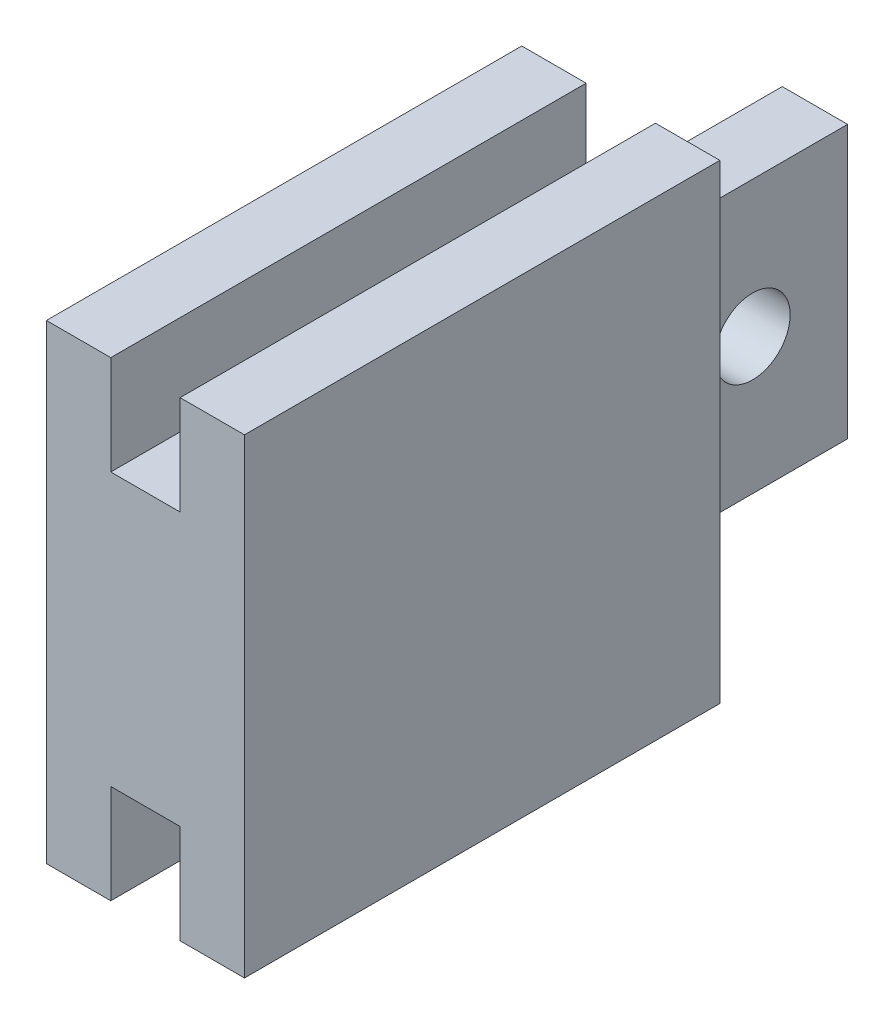
SolidWorks part; units mm, degrees
ref_plane "Front Plane" through (0, 0, 0) normal (1, 0, 0) x (0, 1, 0)
ref_plane "Top Plane" through (0, 0, 0) normal (0, 0, 1) x (0, 1, 0)
ref_plane "Right Plane" through (0, 0, 0) normal (0, 1, 0) x (-1, 0, 0)
sketch "Sketch1" plane through (0, 0, 0) normal (1, 0, 0) x (0, 1, 0)
  line L1 (0, 0) -> (23.75, 0)
  line L2 (0, 0) -> (0, 24)
  line L3 (0, 24) -> (23.75, 24)
  line L4 (23.75, 0) -> (23.75, 24)
  dimension "D1" = 23.75
  dimension "D2" = 24
extrude "Boss-Extrude1" add sketch "Sketch1" against normal blind 10
sketch "Sketch2" plane through (0, 0, 0) normal (0, -1, 0) x (1, 0, 0)
  line L1 (-10, 0) -> (-6.65, 0)
  line L2 (-10, 0) -> (-10, -9.8)
  line L3 (-10, -9.8) -> (-6.65, -9.8)
  line L4 (-6.65, 0) -> (-6.65, -9.8)
  line L5 (0, 0) -> (-3.35, 0)
  line L6 (0, 0) -> (0, -9.8)
  line L7 (0, -9.8) -> (-3.35, -9.8)
  line L8 (-3.35, 0) -> (-3.35, -9.8)
  line L9 (-6.65, -9.8) -> (-3.35, -9.8)
  line L10 (-6.65, -9.8) -> (-6.65, 0)
  line L11 (-6.65, 0) -> (-3.35, 0)
  line L12 (-3.35, -9.8) -> (-3.35, 0)
  line M12 (-10, 0) -> (0, 0)
  dimension "D1" = 9.8
  dimension "D2" = 3.35
  dimension "D3" = 3.35
extrude "Boss-Extrude2" add sketch "Sketch2" against normal through all contours L4 L9 L8 M12 region at (-5, 0, -4.9)
sketch "Sketch3" plane through (0, 0, 0) normal (0, -1, 0) x (1, 0, 0)
  line L0 (-3.35, 20.65) -> (-3.35, 3.35)
  line L1 (0, 24) -> (-10, 24)
  line L2 (0, 24) -> (0, 0)
  line L3 (0, 0) -> (-10, 0)
  line L4 (-10, 24) -> (-10, 0)
  line L5 (-3.35, 3.35) -> (-6.65, 3.35)
  line L6 (-6.65, 20.65) -> (-6.65, 3.35)
  line L7 (-3.35, 20.65) -> (-6.65, 20.65)
  line L9 (-6.65, 20.65) -> (-3.35, 20.65)
  line L10 (-6.65, 20.65) -> (-6.65, 24)
  line L11 (-6.65, 24) -> (-3.35, 24)
  line L12 (-3.35, 20.65) -> (-3.35, 24)
  dimension "D1" = 3.35
extrude "Boss-Extrude3" [suppressed] add sketch "Sketch3" along normal blind 4.9 contours L0 L7 L6 L5 | L10 L9 L12 L11
sketch "Sketch4" plane through (-6.65, 0, 0) normal (-1, 0, 0) x (0, -1, 0)
  line L0 (0, 0) -> (-23.75, 0) construction
  line L1 (-11.875, 0) -> (-23.75, 0)
  line L2 (-11.875, 0) -> (-11.875, -5)
  line L3 (-11.875, -5) -> (-23.75, -5)
  line L4 (-23.75, 0) -> (-23.75, -5)
  circle A0 centre (-11.875, -5) radius 1.9
  dimension "D2" = 3.8
extrude "Cut-Extrude1" cut sketch "Sketch4" against normal up to next contours A0
sketch "Sketch5" plane through (0, 23.75, 0) normal (0, 1, 0) x (-1, 0, 0)
  line L0 (3.25, 20.75) -> (3.25, 3.25)
  line L1 (0, 24) -> (10, 24)
  line L2 (0, 24) -> (0, 0)
  line L3 (0, 0) -> (10, 0)
  line L4 (10, 24) -> (10, 0)
  line L5 (3.25, 3.25) -> (6.75, 3.25)
  line L6 (6.75, 20.75) -> (6.75, 3.25)
  line L7 (3.25, 20.75) -> (6.75, 20.75)
  line L9 (3.25, 20.75) -> (6.75, 20.75)
  line L10 (3.25, 20.75) -> (3.25, 24)
  line L11 (3.25, 24) -> (6.75, 24)
  line L12 (6.75, 20.75) -> (6.75, 24)
  line L13 (3.25, 3.25) -> (6.75, 3.25)
  line L14 (3.25, 3.25) -> (3.25, -9.8)
  line L15 (3.25, -9.8) -> (6.75, -9.8)
  line L16 (6.75, 3.25) -> (6.75, -9.8)
  line M11 (3.35, 0) -> (3.35, -9.8)
  line M12 (3.35, -9.8) -> (6.65, -9.8)
  line M13 (6.65, -9.8) -> (6.65, 0)
  line M14 (6.65, 0) -> (10, 0)
  dimension "D1" = 3.25
extrude "Cut-Extrude2" cut sketch "Sketch5" against normal blind 5 contours L7 L12 L1 L10 | L7 L0 L5 L6 | L16 L5 L14 L3 M14 | L3 M11 M12 M13 region at (-5, 23.75, 12) region at (-5, 23.75, 22.375) region at (-5, 23.75, 1.625) region at (-5, 23.75, -4.9)
ref_plane "Plane1" through (0, 11.875, 0) normal (0, 1, 0) x (1, 0, 0)
mirror "Mirror1" about plane through (0, 11.875, 0) normal (0, 1, 0) of "Cut-Extrude2"
equation "\"whitekey_cutout_length\"= 101.5"
equation "\"key_mount_recess_length\"=50"
equation "\"key_mount_recess_height\"=12.5"
equation "\"key_mount_recess_depth\"=1.5"
equation "\"wall_thickness\"=10"
equation "\"guide_brace_height\"=20"
equation "\"guide_brace_thickness\"=2"
equation "\"dowel_recess_depth\"=10"
equation "\"dowel_recess_offset\"=3.25"
equation "\"base_mount_height\"=40"
equation "\"base_rear_length\"=80"
equation "\"base_front_length\"=111.5"
equation "\"screw_hole_wall_offset\"=7.25"
equation "\"screw_hole_edge_inset\"=\"dowel_recess_depth\"/2"
equation "\"screw_hole_diameter\"=3.8"
equation "\"screw_head_hole_diameter\"=6.7"
equation "\"screw_nut_hole_side_len\"=3.5"
equation "\"screw_shaft_diameter\"=3.5"
equation "\"switch_board_width\"=30"
equation "\"switch_board_wall_offset\"=11.5"
equation "\"heatset_insert_hole_diameter\"=4.8"
equation "\"heatset_insert_hole_depth\"=3.8"
equation "\"D1@Boss-Extrude1\"=\"wall_thickness\""
equation "\"D2@Sketch2\"=\"dowel_recess_offset\"+\"dowel_insert_tolerance\""
equation "\"D3@Sketch2\"=\"dowel_recess_offset\"+\"dowel_insert_tolerance\""
equation "\"D1@Boss-Extrude3\"=\"front_rear_panel_recess_depth\"-\"dowel_insert_tolerance\""
equation "\"D1@Sketch3\"=\"dowel_recess_offset\"+\"dowel_insert_tolerance\""
equation "\"D1@Sketch2\"=\"dowel_recess_depth\"-\"dowel_insert_tolerance\"*2"
equation "\"D1@Sketch4\"=\"screw_hole_edge_inset\""
equation "\"D2@Sketch4\"=\"screw_hole_diameter\""
equation "\"D1@Sketch5\"=\"dowel_recess_offset\""
equation "\"D1@Cut-Extrude2\"=\"front_rear_panel_recess_depth\""
equation "\"screw_nut_recess_offset\"=0.35"
equation "\"screw_head_and_nut_recess_depth\"=2.5"
equation "\"front_rear_panel_width\"=23.75"
equation "\"rod_length_adj\"=0.5"
equation "\"rod_insert_length\"=2.8"
equation "\"D1@Sketch1\"=\"front_rear_panel_width\""
equation "\"switch_board_thickness\"=1.6"
equation "\"front_panel_height\"=24"
equation "\"rod_diameter\"=5"
equation "\"rod_head_diameter\"=8"
equation "\"switch_black_key_mount_height\"=8"
equation "\"switch_white_key_mount_height\"=3"
equation "\"D2@Sketch1\"=\"front_panel_height\""
equation "\"dowel_insert_tolerance\"=0.1"
equation "\"front_rear_panel_recess_depth\"=5"
